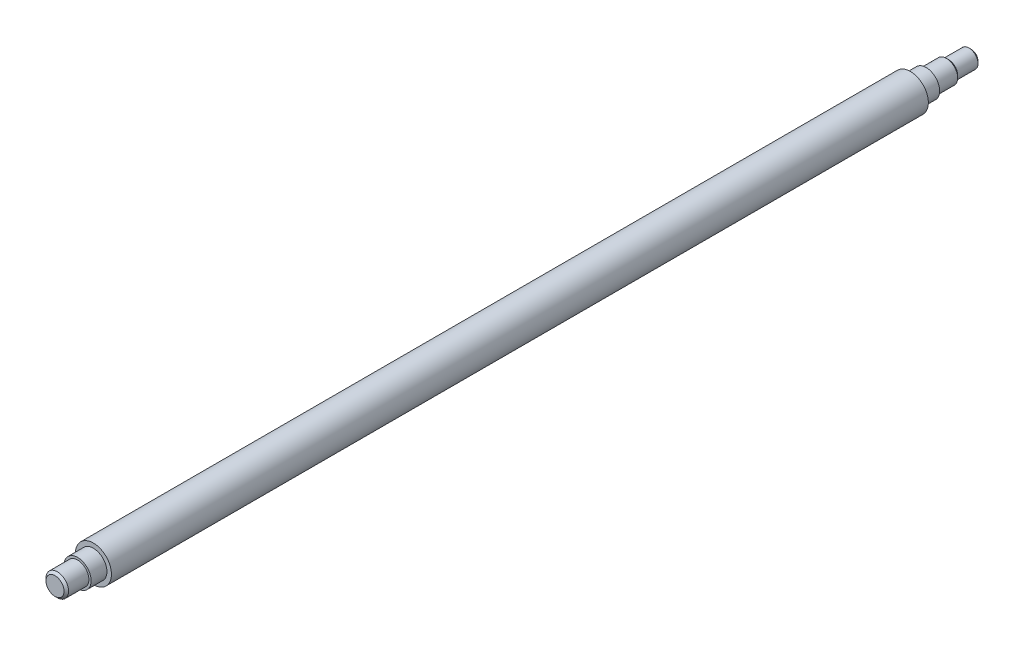
SolidWorks part; units mm, degrees
material "Ductile Iron (SN)"
ref_plane "Front Plane" through (0, 0, 0) normal (0, 0, 1) x (1, 0, 0)
ref_plane "Top Plane" through (0, 0, 0) normal (0, 1, 0) x (1, 0, 0)
ref_plane "Right Plane" through (0, 0, 0) normal (1, 0, 0) x (0, 0, -1)
sketch "Sketch1" plane through (0, 0, 0) normal (0, 0, 1) x (1, 0, 0)
  circle A0 centre (0, 0) radius 8
  dimension "D1" = 16
extrude "Boss-Extrude1" add sketch "Sketch1" along normal blind 362
sketch "Sketch4" plane through (0, 0, 0) normal (0, 0, 1) x (1, 0, 0)
  circle A0 centre (0, 0) radius 6
  dimension "D1" = 12
sketch "Sketch6" plane through (0, 0, 0) normal (0, 0, -1) x (-1, 0, 0)
  circle A0 centre (0, 0) radius 6
  dimension "D1" = 12
extrude "Boss-Extrude2" add sketch "Sketch6" along normal blind 5
sketch "Sketch7" plane through (0, 0, -5) normal (0, 0, -1) x (-1, 0, 0)
  circle A0 centre (0, 0) radius 6
  dimension "D1" = 12
extrude "Boss-Extrude3" add sketch "Sketch7" along normal blind 2
sketch "Sketch8" plane through (0, 0, -7) normal (0, 0, -1) x (-1, 0, 0)
  circle A0 centre (0, 0) radius 5
  dimension "D1" = 10
extrude "Boss-Extrude4" add sketch "Sketch8" along normal blind 10
sketch "Sketch9" plane through (0, 0, -17) normal (0, 0, -1) x (-1, 0, 0)
  circle A0 centre (0, 0) radius 4
  dimension "D1" = 8
extrude "Boss-Extrude5" add sketch "Sketch9" along normal blind 10
chamfer "Chamfer1" distance 1 angle 45 1 edges at (-5, 0, -17)
chamfer "Chamfer2" distance 1 angle 45 1 edges at (-4, 0, -27)
sketch "Sketch10" plane through (0, 0, 362) normal (0, 0, 1) x (1, 0, 0)
  circle A0 centre (0, 0) radius 6
  dimension "D1" = 12
extrude "Boss-Extrude6" add sketch "Sketch10" along normal blind 5
sketch "Sketch11" plane through (0, 0, 367) normal (0, 0, 1) x (1, 0, 0)
  circle A0 centre (0, 0) radius 6
  dimension "D1" = 12
extrude "Boss-Extrude7" add sketch "Sketch11" along normal blind 2
sketch "Sketch12" plane through (0, 0, 369) normal (0, 0, 1) x (1, 0, 0)
  circle A0 centre (0, 0) radius 5
  dimension "D1" = 10
extrude "Boss-Extrude8" add sketch "Sketch12" along normal blind 10
chamfer "Chamfer3" distance 1 angle 45 1 edges at (5, 0, 379)
